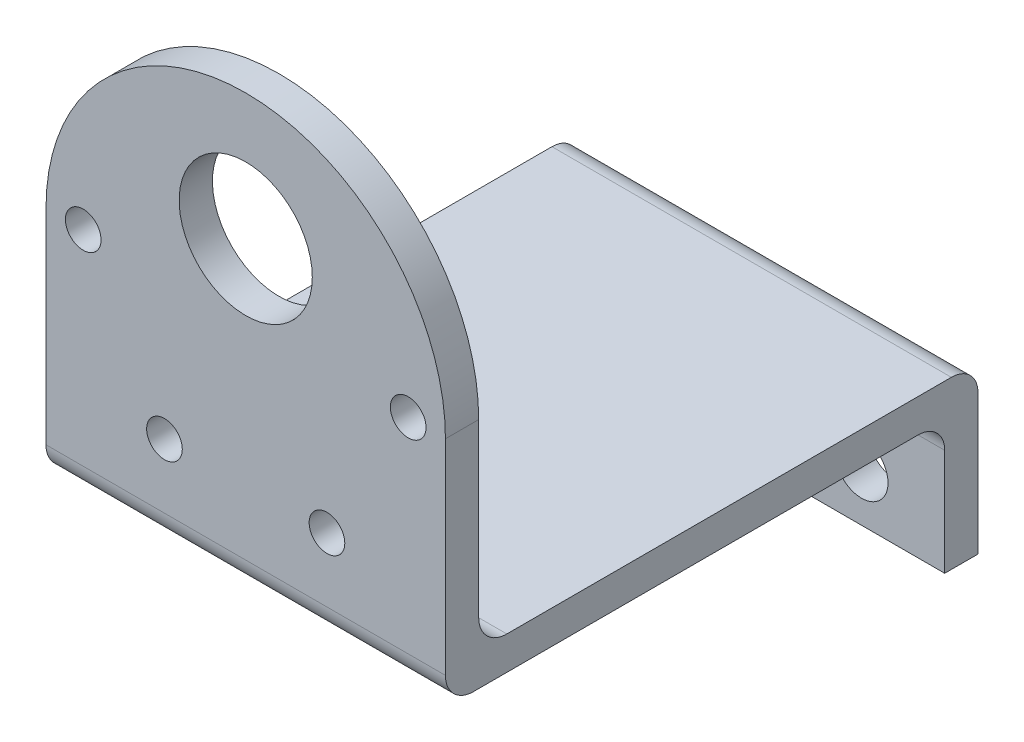
SolidWorks part; units mm, degrees
ref_plane "Front Plane" through (0, 0, 0) normal (0, 0, 1) x (1, 0, 0)
ref_plane "Top Plane" through (0, 0, 0) normal (0, 1, 0) x (1, 0, 0)
ref_plane "Right Plane" through (0, 0, 0) normal (1, 0, 0) x (0, 0, -1)
sketch "Sketch1" plane through (0, 0, 0) normal (1, 0, 0) x (0, 0, -1)
  line L0 (0, 42.0944) -> (0, 6.6753)
  line L1 (2.681, 3.9944) -> (45.085, 3.9944)
  line L3 (0, 42.0944) -> (-3.175, 42.0944)
  line L4 (-3.175, 42.0944) -> (-3.175, 3.5003)
  line L5 (-0.494, 0.8194) -> (41.91, 0.8194)
  line L8 (47.625, 1.4544) -> (47.625, -11.8806)
  line L9 (47.625, -11.8806) -> (44.45, -11.8806)
  line L10 (44.45, -11.8806) -> (44.45, -1.7206)
  arc A2 (-3.175, 3.5003) -> (-0.494, 0.8194) centre (-0.494, 3.5003) ccw
  arc A3 (0, 6.6753) -> (2.681, 3.9944) centre (2.681, 6.6753) ccw
  arc A4 (45.085, 3.9944) -> (47.625, 1.4544) centre (45.085, 1.4544) cw
  arc A5 (41.91, 0.8194) -> (44.45, -1.7206) centre (41.91, -1.7206) cw
  point P14 (46.0375, -11.8806)
  dimension "D2" = 2.54
  dimension "D1" = 3.175
  dimension "D3" = 3.175
  dimension "D4" = 12.7
  dimension "D6" = 50.8
  dimension "D7" = 3.175
  dimension "D5" = 38.1
extrude "Boss-Extrude1" add sketch "Sketch1" along normal blind 38.1 contours L0 A3 L1 A4 L8 L9 L10 A5 L5 A2 L4 L3
hole_wizard "#8 (0.199) Diameter Hole1" positions "Sketch9" profile "Sketch10" hole size "#8" standard "ANSI Inch" end condition through all
sketch "Sketch9" plane through (0, 0, -44.45) normal (0, 0, 1) x (1, 0, 0)
  line L0 (38.1, -11.8806) -> (0, -11.8806) construction
  point P0 (7.9375, -7.1181)
  point P2 (30.1625, -7.1181)
  point P7 (19.05, -11.8806)
  dimension "D1" = 22.225
  dimension "D2" = 4.7625
  dimension "D3" = 11.1125
sketch "Sketch10" plane through (7.9375, -7.1181, -44.45) normal (1, 0, 0) x (0, -1, 0)
  line L0 (0, 0) -> (0, 3.175)
  line L1 (0, 3.175) -> (2.5273, 3.175)
  line L2 (2.5273, 3.175) -> (2.5273, 0)
  line L5 (2.5273, 0) -> (0, 0)
  line L11 (0, -6.35) -> (0, 107.95) construction
  dimension "Thru Hole Dia." = 5.0546
  dimension "Thru Hole Depth" = 3.175
sketch "Sketch11" plane through (0, 0, 3.175) normal (0, 0, 1) x (1, 0, 0)
  line L0 (38.1, 42.0944) -> (0, 42.0944) construction
  line L1 (38.1, 42.0944) -> (38.1, 3.5003) construction
  line L4 (0, 23.0444) -> (0, 42.0944)
  line L5 (0, 42.0944) -> (38.1, 42.0944)
  line L6 (38.1, 23.0444) -> (38.1, 42.0944)
  arc A0 (38.1, 23.0444) -> (0, 23.0444) centre (19.05, 23.0444) ccw
  circle A3 centre (19.05, 30.0444) radius 6.35
  point P5 (19.05, 42.0944)
  line M2 (0, 42.0944) -> (0, 3.5003)
  line M4 (38.1, 3.5003) -> (38.1, 42.0944)
  line M5 (38.1, 42.0944) -> (0, 42.0944)
  dimension "D2" = 7
  dimension "D1" = 12.7
extrude "Cut-Extrude1" cut sketch "Sketch11" against normal through all contours A0 M4 M5 | A0 L5 M2 | A3 | A3 region at (33.8448, 37.8392, 3.175) region at (4.2552, 37.8392, 3.175) region at (19.05, 30.0444, 3.175)
sketch "Sketch12" plane through (0, 0, 3.175) normal (0, 0, 1) x (1, 0, 0)
  circle A0 centre (19.05, 23.0444) radius 15.5 construction
  point P3 (3.55, 23.0444)
  point P6 (11.3, 9.621)
  point P7 (26.8, 9.621)
  point P8 (34.55, 23.0444)
  point P9 (26.8, 36.4678)
  point P10 (11.3, 36.4678)
  point P11 (19.05, 23.0444)
  dimension "D1" = 31
  dimension "D2" = 6
hole_wizard "M3 Clearance Hole1" positions "Sketch13" profile "Sketch14" hole size "M3" standard "ANSI Metric" end condition through all
sketch "Sketch13" plane through (0, 0, 3.175) normal (0, 0, 1) x (1, 0, 0)
  point P0 (3.55, 23.0444)
  point P9 (34.55, 23.0444)
  point P12 (26.8, 9.621)
  point P15 (11.3, 9.621)
sketch "Sketch14" plane through (3.55, 23.0444, 3.175) normal (1, 0, 0) x (0, -1, 0)
  line L0 (0, 0) -> (0, 50.8)
  line L1 (0, 50.8) -> (1.7, 50.8)
  line L2 (1.7, 50.8) -> (1.7, 0)
  line L5 (1.7, 0) -> (0, 0)
  line L11 (0, -6.35) -> (0, 107.95) construction
  dimension "Thru Hole Dia." = 3.4
  dimension "Thru Hole Depth" = 50.8
ref_plane "Plane1" through (19.05, 0, 0) normal (1, 0, 0) x (0, 0, -1)
sketch "Sketch15" plane through (0, 0, -44.45) normal (0, 0, 1) x (1, 0, 0)
  line L0 (19.05, 23.0444) -> (19.05, -11.8806) construction
  line L1 (38.1, -11.8806) -> (0, -11.8806) construction
  arc A1 (0.2117, -3.0014) -> (15.7584, -8.9311) centre (19.05, 23.0444) ccw construction
  arc A2 (-1.255, -5.0293) -> (15.5021, -11.4207) centre (19.05, 23.0444) ccw
  arc A3 (1.6784, -0.9735) -> (16.0147, -6.4415) centre (19.05, 23.0444) ccw
  arc A4 (1.6784, -0.9735) -> (-1.255, -5.0293) centre (0.2117, -3.0014) ccw
  arc A5 (15.5021, -11.4207) -> (16.0147, -6.4415) centre (15.7584, -8.9311) ccw
  circle A6 centre (7.9375, -7.1181) radius 2.5273 construction
  circle A7 centre (7.9375, -7.1181) radius 2.5273
  circle A8 centre (19.05, 30.0444) radius 6.35 construction
  circle A9 centre (19.05, 30.0444) radius 6.35
  point P0 (19.05, 23.0444)
  point P5 (19.05, 23.0444)
  point P8 (7.5947, -6.9896)
  point P16 (8.4866, -4.6512)
  dimension "D1" = 30
equation "\"D3@Sketch1\"=\"D1@Sketch1\""
equation "\"D7@Sketch1\"=\"D1@Sketch1\""
equation "\"D3@Sketch9\"=\"D1@Sketch9\"/2"
